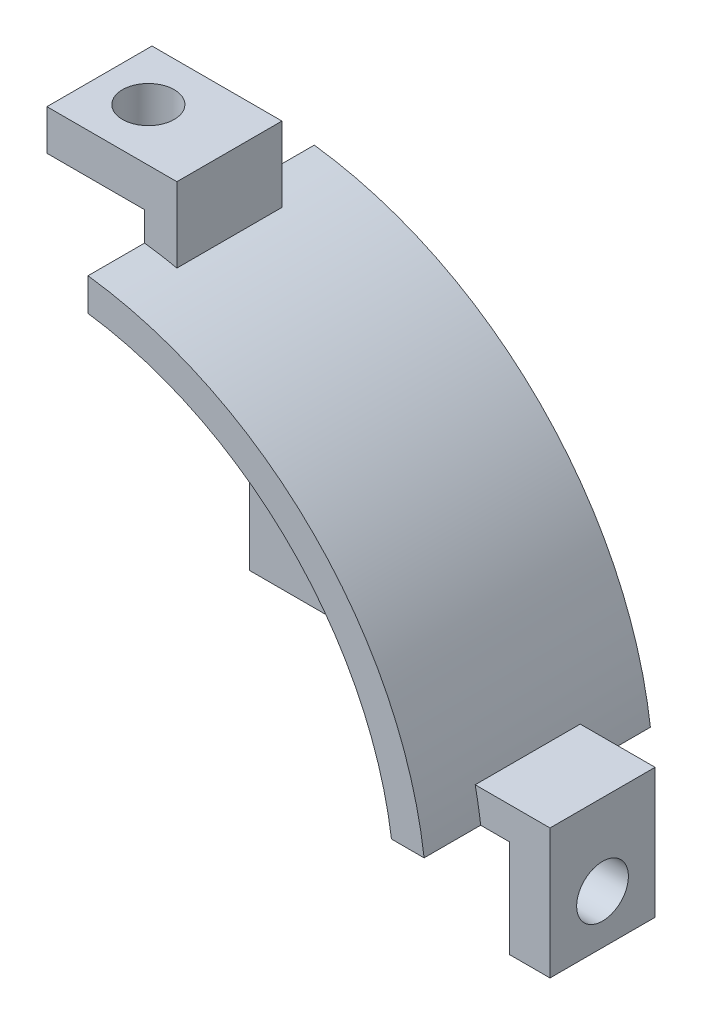
SolidWorks part; units mm, degrees
ref_plane "Front Plane" through (0, 0, 0) normal (0, 0, 1) x (1, 0, 0)
ref_plane "Top Plane" through (0, 0, 0) normal (0, 1, 0) x (1, 0, 0)
ref_plane "Right Plane" through (0, 0, 0) normal (1, 0, 0) x (0, 0, -1)
sketch "Sketch1" plane through (0, 0, 0) normal (0, 0, 1) x (1, 0, 0)
  line L0 (3.025, 25.6) -> (-3.025, 25.6)
  line L1 (25.6, -3.025) -> (25.6, 3.025)
  line L2 (-3.025, 25.6) -> (-3.025, 28.1)
  line L3 (-3.025, 28.1) -> (3.025, 28.1)
  line L4 (25.6, -3.025) -> (28.1, -3.025)
  line L5 (28.1, -3.025) -> (28.1, 3.025)
  circle A0 centre (0, 0) radius 16 construction
  circle A1 centre (0, 0) radius 25.6 construction
  arc A2 (3.025, 25.6) -> (25.6, 3.025) centre (3.025, 3.025) cw
  arc A3 (3.025, 28.1) -> (28.1, 3.025) centre (4.7678, 4.7678) cw
  point P7 (0, 25.6)
  point P10 (25.6, 0)
  dimension "D1" = 32
  dimension "D2" = 9.6
  dimension "D5" = 2.5
  dimension "D8" = 6.05
  dimension "D3" = 6.05
  dimension "D4" = 6.05
  dimension "D6" = 2.5
  dimension "D7" = 6.05
extrude "Boss-Extrude1" add sketch "Sketch1" along normal blind 14.5
hole_wizard "M3 Clearance Hole1" positions "Sketch2" profile "Sketch3" hole size "M3" standard "ANSI Metric" end condition up to next
sketch "Sketch2" plane through (0, 28.1, 0) normal (0, 1, 0) x (1, 0, 0)
  point P0 (0, -7.25)
sketch "Sketch3" plane through (0, 28.1, 7.25) normal (1, 0, 0) x (0, 0, 1)
  line L0 (0, 0) -> (0, 2.5)
  line L1 (0, 2.5) -> (1.6, 2.5)
  line L2 (1.6, 2.5) -> (1.6, 0)
  line L5 (1.6, 0) -> (0, 0)
  line L11 (0, -6.35) -> (0, 107.95) construction
  dimension "Thru Hole Dia." = 3.2
  dimension "Thru Hole Depth" = 2.5
hole_wizard "M3 Clearance Hole2" positions "Sketch4" profile "Sketch5" hole size "M3" standard "ANSI Metric" end condition up to next
sketch "Sketch4" plane through (28.1, 0, 0) normal (1, 0, 0) x (0, 0, -1)
  point P0 (-7.25, 0)
sketch "Sketch5" plane through (28.1, 0, 7.25) normal (0, 1, 0) x (0, 0, -1)
  line L0 (0, 0) -> (0, 2.5)
  line L1 (0, 2.5) -> (1.6, 2.5)
  line L2 (1.6, 2.5) -> (1.6, 0)
  line L5 (1.6, 0) -> (0, 0)
  line L11 (0, -6.35) -> (0, 107.95) construction
  dimension "Thru Hole Dia." = 3.2
  dimension "Thru Hole Depth" = 2.5
sketch "Sketch6" plane through (0, 28.1, 0) normal (0, 1, 0) x (1, 0, 0)
  line L0 (-3.025, -14.5) -> (-3.025, 0) construction
  line L1 (3.025, -14.5) -> (-3.025, -14.5)
  line L2 (3.025, -14.5) -> (3.025, -10.5)
  line L3 (3.025, -10.5) -> (-3.025, -10.5)
  line L4 (-3.025, -14.5) -> (-3.025, -10.5)
  line L5 (3.025, -14.5) -> (3.025, 0) construction
  line L6 (-3.025, 0) -> (3.025, 0)
  line L7 (-3.025, 0) -> (-3.025, -4)
  line L8 (-3.025, -4) -> (3.025, -4)
  line L9 (3.025, 0) -> (3.025, -4)
  dimension "D1" = 4
  dimension "D2" = 4
extrude "Cut-Extrude1" cut sketch "Sketch6" against normal blind 10
sketch "Sketch7" plane through (28.1, 0, 0) normal (1, 0, 0) x (0, 0, -1)
  line L0 (-14.5, 3.025) -> (0, 3.025) construction
  line L1 (-14.5, -3.025) -> (-10.5, -3.025)
  line L2 (-14.5, -3.025) -> (-14.5, 3.025)
  line L3 (-14.5, 3.025) -> (-10.5, 3.025)
  line L4 (-10.5, -3.025) -> (-10.5, 3.025)
  line L5 (-14.5, -3.025) -> (0, -3.025) construction
  line L6 (0, 3.025) -> (-4, 3.025)
  line L7 (0, 3.025) -> (0, -3.025)
  line L8 (0, -3.025) -> (-4, -3.025)
  line L9 (-4, 3.025) -> (-4, -3.025)
  dimension "D1" = 4
  dimension "D2" = 4
extrude "Cut-Extrude2" cut sketch "Sketch7" against normal blind 10
sketch "Sketch8" plane through (0, 0, 0) normal (0, 0, -1) x (-1, 0, 0)
  line L6 (-31.0354, 3.015) -> (-3.015, 3.015)
  line L7 (-3.015, 3.015) -> (-3.015, 31.0354)
  arc A1 (-3.015, 31.0354) -> (-31.0354, 3.015) centre (0, 0) ccw
  point P5 (0, 0)
  point P8 (0, 0)
extrude "Boss-Extrude7" add sketch "Sketch8" against normal blind 14
sketch "Sketch14" plane through (0, 0, 14) normal (0, 0, 1) x (1, 0, 0)
  line L1 (-15.0546, 40.0119) -> (41.948, 40.0119)
  line L2 (-15.0546, 40.0119) -> (-15.0546, -1.1806)
  line L3 (-15.0546, -1.1806) -> (41.948, -1.1806)
  line L4 (41.948, 40.0119) -> (41.948, -1.1806)
extrude "Cut-Extrude4" cut sketch "Sketch14" along normal blind 15
sketch "Sketch15" plane through (0, 0, 14) normal (0, 0, 1) x (1, 0, 0)
  line L0 (3.015, 14) -> (3.015, 25.6) construction
  line L1 (25.6, 3.015) -> (14, 3.015) construction
  line L2 (3.015, 21.7924) -> (3.015, 3.015)
  line L3 (3.015, 3.015) -> (21.7924, 3.015)
  arc A0 (3.015, 21.7924) -> (21.7924, 3.015) centre (0, 0) cw
  circle A1 centre (0, 0) radius 20 construction
  dimension "D1" = 2
extrude "Cut-Extrude5" cut sketch "Sketch15" against normal blind 10
sketch "Sketch16" plane through (0, 0, 14) normal (0, 0, 1) x (1, 0, 0)
  line L0 (5.015, 23.4702) -> (5.015, 28.1)
  line L1 (23.4702, 5.015) -> (28.1, 5.015)
  line L7 (3.015, 21.7924) -> (3.015, 31.0354) construction
  line L8 (31.0354, 3.015) -> (21.7924, 3.015) construction
  line L9 (28.1, 3.015) -> (28.1, 5.015)
  line L10 (3.015, 28.1) -> (5.015, 28.1)
  line L11 (3.015, 28.1) -> (3.015, 36.2072)
  line L12 (3.015, 36.2072) -> (34.3005, 28.1)
  line L13 (34.3005, 28.1) -> (32.4104, 3.015)
  line L14 (32.4104, 3.015) -> (28.1, 3.015)
  line L15 (28.1, -3.025) -> (28.1, 3.015) construction
  arc A0 (23.4702, 5.015) -> (5.015, 23.4702) centre (0, 0) ccw
  arc A1 (21.7924, 3.015) -> (3.015, 21.7924) centre (0, 0) ccw construction
  point P18 (0, 0)
  dimension "D1" = 2
  dimension "D2" = 2
  dimension "D3" = 2
  dimension "D4" = 0
extrude "Cut-Extrude8" cut sketch "Sketch16" against normal blind 20
sketch "Sketch17" plane through (28.1, 0, 0) normal (1, 0, 0) x (0, 0, -1)
  line L1 (0, 5.015) -> (-4, 5.015)
  line L2 (0, 5.015) -> (0, 3.015)
  line L3 (0, 3.015) -> (-4, 3.015)
  line L4 (-4, 5.015) -> (-4, 3.015)
  line L5 (-14, 5.015) -> (-10.5, 5.015)
  line L6 (-14, 5.015) -> (-14, 3.015)
  line L7 (-14, 3.015) -> (-10.5, 3.015)
  line L8 (-10.5, 5.015) -> (-10.5, 3.015)
extrude "Cut-Extrude9" cut sketch "Sketch17" against normal up to surface (4.6298 mm away) up to face at (15.6066, 15.6066, 7)
sketch "Sketch18" plane through (0, 28.1, 0) normal (0, 1, 0) x (1, 0, 0)
  line L1 (5.015, -14) -> (3.015, -14)
  line L2 (5.015, -14) -> (5.015, -10.5)
  line L3 (5.015, -10.5) -> (3.015, -10.5)
  line L4 (3.015, -14) -> (3.015, -10.5)
  line L5 (5.015, 0) -> (3.015, 0)
  line L6 (5.015, 0) -> (5.015, -4)
  line L7 (5.015, -4) -> (3.015, -4)
  line L8 (3.015, 0) -> (3.015, -4)
extrude "Cut-Extrude10" cut sketch "Sketch18" against normal up to surface (4.2901 mm away) up to face at (19.8466, 9.3786, 7.125)
